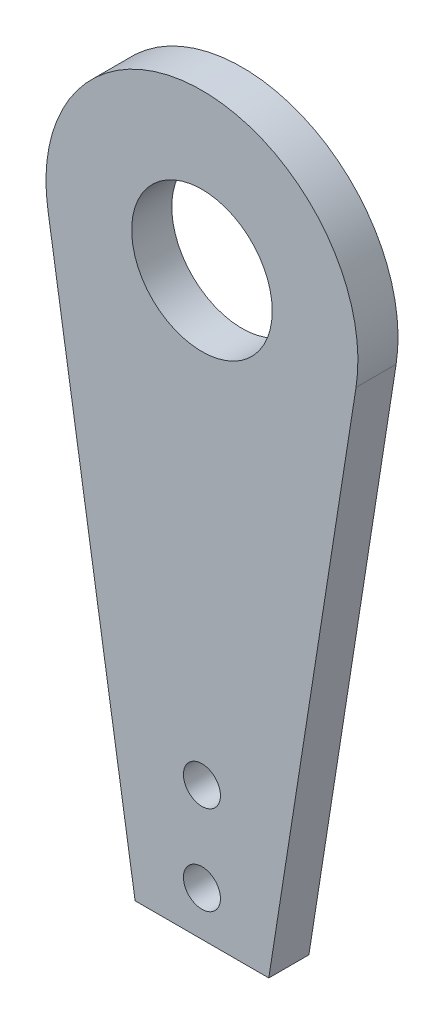
SolidWorks part; units mm, degrees
ref_plane "Front Plane" through (0, 0, 0) normal (0, 0, 1) x (1, 0, 0)
ref_plane "Top Plane" through (0, 0, 0) normal (0, 1, 0) x (1, 0, 0)
ref_plane "Right Plane" through (0, 0, 0) normal (1, 0, 0) x (0, 0, -1)
ref_axis "X Axis" through (-88.99, 0, 0) along (1, 0, 0)
ref_axis "Y Axiz" through (0, 0, 55) along (0, 0, -1)
ref_axis "Z Axis" through (0, 55, 0) along (0, -1, 0)
sketch "Sketch1" plane through (0, 0, 0) normal (0, 0, 1) x (1, 0, 0)
  line L0 (-7.5, -5) -> (7.5, -5)
  line L1 (-7.5, -5) -> (-17.2878, 57.2832)
  line L2 (0, -5) -> (0, 0) construction
  line L4 (17.2878, 57.2832) -> (7.5, -5)
  line L5 (0, 0) -> (0, 60) construction
  circle A0 centre (0, 0) radius 2.075
  circle A2 centre (0, 60) radius 7.8875
  arc A3 (17.2878, 57.2832) -> (-17.2878, 57.2832) centre (0, 60) ccw
  circle A4 centre (0, 10) radius 2.075
  dimension "D1" = 4.15
  dimension "D3" = 5
  dimension "D4" = 15.775
  dimension "D5" = 35
  dimension "D2" = 10
  dimension "D6" = 60
  dimension "D7" = 15
extrude "Boss-Extrude2" add sketch "Sketch1" along normal blind 4.5
